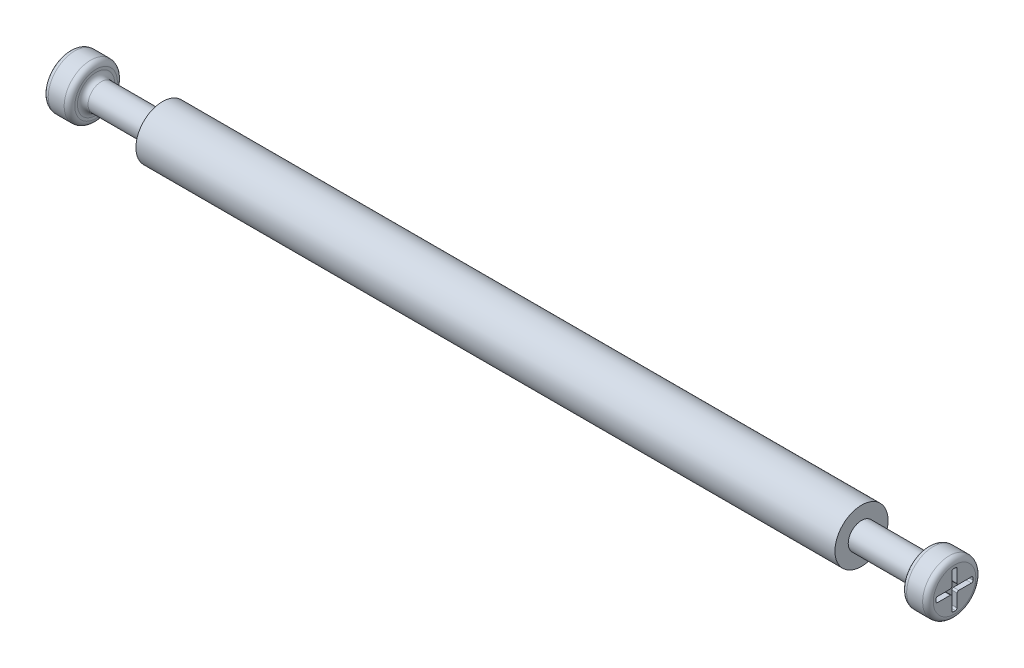
SolidWorks part; units mm, degrees
ref_plane "Front Plane" through (0, 0, 0) normal (0, 0, 1) x (1, 0, 0)
ref_plane "Top Plane" through (0, 0, 0) normal (0, 1, 0) x (1, 0, 0)
ref_plane "Right Plane" through (0, 0, 0) normal (1, 0, 0) x (0, 0, -1)
sketch "Sketch1" plane through (0, 0, 0) normal (1, 0, 0) x (0, 0, -1)
  circle A0 centre (0, 0) radius 12.7
extrude "Boss-Extrude1" add sketch "Sketch1" along normal blind 167.005 and the other way blind 167.005
sketch "Sketch2" plane through (-167.005, 0, 0) normal (-1, 0, 0) x (0, 0, 1)
  circle A0 centre (0, 0) radius 6.35
extrude "Boss-Extrude2" add sketch "Sketch2" along normal blind 31.75
sketch "Sketch3" plane through (-198.755, 0, 0) normal (-1, 0, 0) x (0, 0, 1)
  circle A0 centre (0, 0) radius 12.7
extrude "Boss-Extrude3" add sketch "Sketch3" along normal blind 12.7
fillet "Fillet1" radius 2.54 3 edges at (-211.455, 0, 12.7) (-198.755, 0, 12.7) (-198.755, 0, 6.35)
sketch "Sketch4" plane through (-211.455, 0, 0) normal (-1, 0, 0) x (0, 0, 1)
  line L0 (-0.5536, 9.0753) -> (0.4624, 9.0753)
  line L1 (-1.3156, 8.3133) -> (-1.3156, 2.2173)
  line L2 (-0.5536, -8.7047) -> (0.4624, -8.7047)
  line L3 (1.2244, 8.3133) -> (1.2244, 2.2173)
  line L4 (-8.1736, 1.4553) -> (-2.0776, 1.4553)
  line L5 (-8.9356, 0.6933) -> (-8.9356, -0.3227)
  line L6 (-8.1736, -1.0847) -> (-2.0776, -1.0847)
  line L7 (8.8444, 0.6933) -> (8.8444, -0.3227)
  line L8 (1.2244, -1.8467) -> (1.2244, -7.9427)
  line L9 (-1.3156, -1.8467) -> (-1.3156, -7.9427)
  line L10 (1.9864, -1.0847) -> (8.0824, -1.0847)
  line L11 (1.9864, 1.4553) -> (8.0824, 1.4553)
  arc A0 (-8.9356, -0.3227) -> (-8.1736, -1.0847) centre (-8.1736, -0.3227) ccw
  arc A1 (-1.3156, -1.8467) -> (-2.0776, -1.0847) centre (-2.0776, -1.8467) ccw
  arc A2 (1.2244, -1.8467) -> (1.9864, -1.0847) centre (1.9864, -1.8467) cw
  arc A3 (-0.5536, -8.7047) -> (-1.3156, -7.9427) centre (-0.5536, -7.9427) cw
  arc A4 (0.4624, -8.7047) -> (1.2244, -7.9427) centre (0.4624, -7.9427) ccw
  arc A5 (8.8444, 0.6933) -> (8.0824, 1.4553) centre (8.0824, 0.6933) ccw
  arc A6 (8.8444, -0.3227) -> (8.0824, -1.0847) centre (8.0824, -0.3227) cw
  arc A7 (-1.3156, 8.3133) -> (-0.5536, 9.0753) centre (-0.5536, 8.3133) cw
  arc A8 (-8.9356, 0.6933) -> (-8.1736, 1.4553) centre (-8.1736, 0.6933) cw
  arc A9 (1.2244, 8.3133) -> (0.4624, 9.0753) centre (0.4624, 8.3133) ccw
  arc A10 (1.9864, 1.4553) -> (1.2244, 2.2173) centre (1.9864, 2.2173) cw
  arc A11 (-1.3156, 2.2173) -> (-2.0776, 1.4553) centre (-2.0776, 2.2173) cw
  point P0 (-0.0456, 0.1853)
  point P5 (-0.0456, 0.1853)
  dimension "D1" = 0.762
  dimension "D2" = 0.762
  dimension "D3" = 0.762
extrude "Cut-Extrude1" cut sketch "Sketch4" against normal blind 2.54
mirror "Mirror1" about plane through (0, 0, 0) normal (1, 0, 0) of "Boss-Extrude2", "Boss-Extrude3"
fillet "Fillet2" radius 2.54 3 edges at (198.755, 0, 6.35) (198.755, 0, 12.7) (211.455, 0, 12.7)
sketch "Sketch5" plane through (211.455, 0, 0) normal (1, 0, 0) x (0, 0, -1)
  line L0 (-0.5451, 8.8159) -> (0.4709, 8.8159)
  line L1 (-1.3071, 8.0539) -> (-1.3071, 1.9579)
  line L2 (-0.5451, -8.9641) -> (0.4709, -8.9641)
  line L3 (1.2329, 8.0539) -> (1.2329, 1.9579)
  line L4 (-8.1651, 1.1959) -> (-2.0691, 1.1959)
  line L5 (-8.9271, 0.4339) -> (-8.9271, -0.5821)
  line L6 (-8.1651, -1.3441) -> (-2.0691, -1.3441)
  line L7 (8.8529, 0.4339) -> (8.8529, -0.5821)
  line L8 (1.2329, -2.1061) -> (1.2329, -8.2021)
  line L9 (-1.3071, -2.1061) -> (-1.3071, -8.2021)
  line L10 (1.9949, -1.3441) -> (8.0909, -1.3441)
  line L11 (1.9949, 1.1959) -> (8.0909, 1.1959)
  arc A0 (-8.9271, -0.5821) -> (-8.1651, -1.3441) centre (-8.1651, -0.5821) ccw
  arc A1 (-1.3071, -2.1061) -> (-2.0691, -1.3441) centre (-2.0691, -2.1061) ccw
  arc A2 (1.2329, -2.1061) -> (1.9949, -1.3441) centre (1.9949, -2.1061) cw
  arc A3 (-0.5451, -8.9641) -> (-1.3071, -8.2021) centre (-0.5451, -8.2021) cw
  arc A4 (0.4709, -8.9641) -> (1.2329, -8.2021) centre (0.4709, -8.2021) ccw
  arc A5 (8.8529, 0.4339) -> (8.0909, 1.1959) centre (8.0909, 0.4339) ccw
  arc A6 (8.8529, -0.5821) -> (8.0909, -1.3441) centre (8.0909, -0.5821) cw
  arc A7 (-1.3071, 8.0539) -> (-0.5451, 8.8159) centre (-0.5451, 8.0539) cw
  arc A8 (-8.9271, 0.4339) -> (-8.1651, 1.1959) centre (-8.1651, 0.4339) cw
  arc A9 (1.2329, 8.0539) -> (0.4709, 8.8159) centre (0.4709, 8.0539) ccw
  arc A10 (1.9949, 1.1959) -> (1.2329, 1.9579) centre (1.9949, 1.9579) cw
  arc A11 (-1.3071, 1.9579) -> (-2.0691, 1.1959) centre (-2.0691, 1.9579) cw
  point P0 (-0.0371, -0.0741)
  point P5 (-0.0371, -0.0741)
  dimension "D1" = 0.762
  dimension "D2" = 0.762
  dimension "D3" = 0.762
extrude "Cut-Extrude2" cut sketch "Sketch5" against normal blind 2.54
